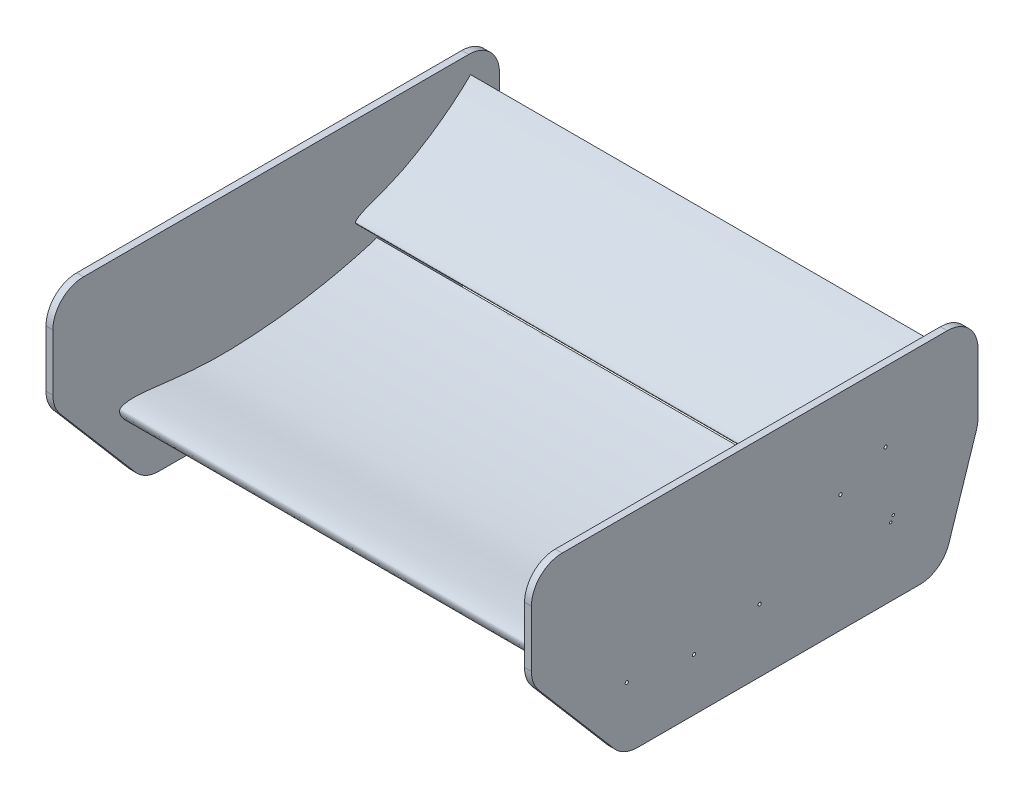
SolidWorks part; units mm, degrees
ref_plane "Front Plane" through (0, 0, 0) normal (0, 0, 1) x (1, 0, 0)
ref_plane "Top Plane" through (0, 0, 0) normal (0, 1, 0) x (1, 0, 0)
ref_plane "Right Plane" through (0, 0, 0) normal (1, 0, 0) x (0, 0, -1)
ref_plane "Soft Top Limit" through (0, 1174.6, 0) normal (0, 1, 0) x (1, 0, 0)
ref_plane "Soft Rear Limit" through (0, 0, -1192.975) normal (0, 0, 1) x (1, 0, 0)
ref_plane "Soft Right Limit" through (-501.65, 0, 0) normal (1, 0, 0) x (0, 0, -1)
ref_plane "Soft Left Limit" through (501.65, 0, 0) normal (1, 0, 0) x (0, 0, -1)
ref_plane "Soft Front Limit" through (0, 0, -165.1) normal (0, 0, 1) x (1, 0, 0)
ref_plane "Slant Limit" through (0, 528.6251, -619.2711) normal (0, -0.6492, 0.7606) x (1, 0, 0)
ref_plane "Bottom" through (0, 476.25, 0) normal (0, 1, 0) x (1, 0, 0)
ref_plane "Midplane" through (0, 0, 0) normal (1, 0, 0) x (0, 0, -1)
curve "Imported Airfoil Curve"
  spline degree 3 poles (0, 2520.0207, 6.126) (0, 2544.889, -1.81) (0, 2521.8965, 7.8839) (0, 2505.3253, 17.7145) (0, 2467.7144, 38.5723) (0, 2424.2142, 62.3813) (0, 2368.0949, 87.8078) (0, 2301.3729, 113.3478) (0, 2223.8362, 140.5377) (0, 2136.6129, 169.2441) (0, 2040.932, 199.097) (0, 1938.2341, 229.6055) (0, 1829.9414, 260.0781) (0, 1717.5266, 289.8586) (0, 1602.4273, 318.1375) (0, 1486.0259, 343.9752) (0, 1369.6902, 366.5754) (0, 1254.3666, 384.7865) (0, 1140.5393, 397.0034) (0, 1028.6357, 403.0127) (0, 919.0585, 402.9406) (0, 812.3986, 397.0375) (0, 709.2785, 385.5985) (0, 610.4299, 369.039) (0, 516.5862, 348.1086) (0, 428.5874, 323.3415) (0, 347.2653, 295.2055) (0, 273.332, 264.2656) (0, 207.4209, 231.0894) (0, 150.0337, 196.3024) (0, 101.596, 160.572) (0, 62.3674, 124.65) (0, 32.4977, 89.3959) (0, 12.0597, 55.6746) (0, 1.683, 26.6201) (0, -0.5567, 6.5526) (0, 0.5894, -3.9947) (0, 1.6947, -9.1451) (0, 2.8711, -12.4915) (0, 3.9449, -14.9776) (0, 4.8993, -16.669) (0, 5.9763, -18.2433) (0, 7.3264, -19.6365) (0, 8.8595, -20.9434) (0, 11.1868, -22.7306) (0, 14.6073, -24.7406) (0, 20.085, -27.4067) (0, 26.8353, -29.9257) (0, 44.6446, -35.1819) (0, 77.8093, -38.8998) (0, 130.2841, -38.2927) (0, 196.3018, -31.4611) (0, 276.2192, -18.4434) (0, 370.8288, 0.8611) (0, 480.7331, 24.811) (0, 605.9792, 50.0099) (0, 745.0759, 74.1542) (0, 895.4497, 95.0846) (0, 1053.6786, 110.004) (0, 1215.6439, 118.3392) (0, 1377.6893, 121.6348) (0, 1537.1174, 120.5125) (0, 1691.5141, 115.2051) (0, 1838.3121, 105.7388) (0, 1975.028, 93.0069) (0, 2099.5942, 78.4581) (0, 2210.5746, 63.1262) (0, 2306.3634, 48.0168) (0, 2387.2069, 33.7158) (0, 2449.0745, 22.0129) (0, 2499.1865, 10.4993) (0, 2520.0207, 6.126) (0, 2544.889, -1.81) (0, 2521.8965, 7.8839) knots -0.016237 -0.007308 -0.001841 0 0.001813 0.006911 0.014576 0.024172 0.035572 0.049013 0.064513 0.081849 0.100772 0.120997 0.142228 0.164173 0.186537 0.209023 0.231367 0.25332 0.274804 0.295858 0.316449 0.336531 0.356033 0.374893 0.39299 0.410197 0.426388 0.441459 0.455334 0.467938 0.479236 0.489204 0.497851 0.505194 0.511308 0.515097 0.516441 0.517273 0.51806 0.518436 0.518797 0.519154 0.519508 0.519887 0.520289 0.52116 0.522116 0.52372 0.525214 0.532575 0.542381 0.554776 0.569931 0.588005 0.609188 0.633329 0.660001 0.688743 0.718873 0.749543 0.780127 0.810209 0.839387 0.867183 0.893104 0.91676 0.937874 0.956199 0.971544 0.983763 0.992692 0.998159 1 1.001813 1.006911 1.014576 periodic
sketch "Airfoils Sketch" plane through (0, 0, 0) normal (1, 0, 0) x (0, 0, -1)
  line L0 (165.1, 1174.6) -> (165.1, 1060.6753) construction
  line L1 (165.1, 1060.6753) -> (663.9798, 476.25) construction
  line L2 (663.9798, 476.25) -> (1192.975, 476.25) construction
  line L3 (1192.975, 476.25) -> (1192.975, 1174.6) construction
  line L4 (1192.975, 1174.6) -> (165.1, 1174.6) construction
  line L5 (509.9361, 1174.6) -> (-509.9361, 1174.6) construction
  line L6 (165.1, 67.0076) -> (165.1, -67.0076) construction
  line L7 (364.7288, 826.8151) -> (873.8134, 230.4351) construction
  line L8 (279.3831, 476.25) -> (-279.3831, 476.25) construction
  line L9 (1192.975, 353.2696) -> (1192.975, -353.2696) construction
  line L10 (414.7055, 818.0274) -> (401.202, 972.3726) construction
  line L11 (945.202, 874.5029) -> (933.446, 1008.8748) construction
  line L12 (939.324, 941.6889) -> (407.9538, 895.2) construction
  line L13 (306.3538, 895.2) -> (1192.975, 895.2) construction
  line L14 (866.0383, 1036.8746) -> (926.5682, 940.0065) construction
  line L15 (1102.685, 1185.4108) -> (1163.8108, 1087.5892) construction
  line L16 (1133.2479, 1136.5) -> (896.3033, 988.4406) construction
  line L21 (176.2614, 1047.6) -> (1192.975, 1047.6) construction
  spline S0 degree 3 poles (935.2529, 940.0507) (940.3147, 942.1548) (935.6767, 939.7163) (932.3848, 937.3638) (924.8872, 932.3286) (916.21, 926.5709) (904.9213, 920.2497) (891.4161, 913.7156) (875.6775, 906.6433) (857.9391, 899.0809) (838.4515, 891.1278) (817.5075, 882.9123) (795.3921, 874.6046) (772.4019, 866.3681) (748.8232, 858.3979) (724.9284, 850.9153) (700.9897, 844.1113) (677.1845, 838.2437) (653.5854, 833.657) (630.2782, 830.4035) (607.3492, 828.4639) (584.9266, 827.7965) (563.1459, 828.3505) (542.1676, 830.0521) (522.1586, 832.7575) (503.3041, 836.37) (485.7865, 840.8065) (469.765, 845.9615) (455.382, 851.7275) (442.7539, 857.9825) (431.9816, 864.5947) (423.1327, 871.4111) (416.2539, 878.2548) (411.376, 884.946) (408.6865, 890.8402) (407.8599, 894.9991) (407.9116, 897.2265) (408.051, 898.3239) (408.2374, 899.0451) (408.4178, 899.5844) (408.5873, 899.9553) (408.7846, 900.3039) (409.0422, 900.6195) (409.3397, 900.9203) (409.7947, 901.3358) (410.4746, 901.8174) (411.5732, 902.4729) (412.9407, 903.1204) (416.5733, 904.5379) (423.4463, 905.9074) (434.4368, 906.7165) (448.3721, 906.4646) (465.3261, 905.1664) (485.4664, 902.8148) (508.8897, 899.7641) (535.5455, 896.7257) (565.0805, 894.155) (596.9177, 892.4579) (630.2914, 892.1587) (664.3294, 893.3038) (698.2942, 895.5048) (731.6326, 898.5836) (763.8436, 902.4482) (794.3904, 907.0475) (822.7695, 912.1503) (848.5739, 917.4165) (871.5218, 922.6042) (891.2949, 927.4743) (907.9553, 931.9087) (920.6916, 935.461) (930.9716, 938.764) (935.2529, 940.0507) (940.3147, 942.1548) (935.6767, 939.7163) knots -0.016237 -0.007308 -0.001841 0 0.001813 0.006911 0.014576 0.024172 0.035572 0.049013 0.064513 0.081849 0.100772 0.120997 0.142228 0.164173 0.186537 0.209023 0.231367 0.25332 0.274804 0.295858 0.316449 0.336531 0.356033 0.374893 0.39299 0.410197 0.426388 0.441459 0.455334 0.467938 0.479236 0.489204 0.497851 0.505194 0.511308 0.515097 0.516441 0.517273 0.51806 0.518436 0.518797 0.519154 0.519508 0.519887 0.520289 0.52116 0.522116 0.52372 0.525214 0.532575 0.542381 0.554776 0.569931 0.588005 0.609188 0.633329 0.660001 0.688743 0.718873 0.749543 0.780127 0.810209 0.839387 0.867183 0.893104 0.91676 0.937874 0.956199 0.971544 0.983763 0.992692 0.998159 1 1.001813 1.006911 1.014576 only from (939.324, 941.6889) to (939.324, 941.6889)
  spline S1 degree 3 poles (1131.7374, 1134.7673) (1133.5995, 1136.953) (1132.0147, 1134.712) (1131.0377, 1132.8312) (1128.7359, 1128.6983) (1126.0553, 1123.9476) (1122.2899, 1118.3128) (1117.5406, 1112.0516) (1111.8769, 1105.0082) (1105.3965, 1097.2604) (1098.1926, 1088.9143) (1090.3713, 1080.0994) (1082.0253, 1070.9629) (1073.254, 1061.6516) (1064.1447, 1052.3247) (1054.7721, 1043.1501) (1045.2175, 1034.2818) (1035.5025, 1025.8823) (1025.5791, 1018.1297) (1015.4749, 1011.0686) (1005.2348, 1004.7108) (994.9285, 999.0671) (984.6313, 994.1461) (974.4357, 989.9515) (964.4538, 986.456) (954.795, 983.6583) (945.5642, 981.5631) (936.8608, 980.159) (928.7768, 979.4298) (921.3956, 979.3461) (914.7955, 979.8704) (909.0446, 980.9475) (904.2067, 982.5058) (900.3389, 984.4687) (897.682, 986.58) (896.3072, 988.3245) (895.8017, 989.3763) (895.6058, 989.9216) (895.5213, 990.3026) (895.4772, 990.5972) (895.4681, 990.8106) (895.4773, 991.0202) (895.5225, 991.2288) (895.5898, 991.4399) (895.7034, 991.742) (895.9061, 992.1285) (896.263, 992.6957) (896.7472, 993.3231) (898.1055, 994.8485) (900.9876, 997.1221) (905.9247, 1000.1133) (912.4884, 1003.3096) (920.7099, 1006.7355) (930.6689, 1010.4274) (942.3265, 1014.5737) (955.4898, 1019.4945) (969.8856, 1025.3183) (985.1482, 1032.0973) (1000.7954, 1039.894) (1016.4092, 1048.5229) (1031.7378, 1057.6271) (1046.5653, 1066.992) (1060.6797, 1076.4556) (1073.8427, 1085.8664) (1085.8742, 1094.9966) (1096.6653, 1103.5909) (1106.1418, 1111.4691) (1114.2121, 1118.4443) (1120.9333, 1124.4758) (1126.0328, 1129.1625) (1130.0452, 1133.1487) (1131.7374, 1134.7673) (1133.5995, 1136.953) (1132.0147, 1134.712) knots -0.016237 -0.007308 -0.001841 0 0.001813 0.006911 0.014576 0.024172 0.035572 0.049013 0.064513 0.081849 0.100772 0.120997 0.142228 0.164173 0.186537 0.209023 0.231367 0.25332 0.274804 0.295858 0.316449 0.336531 0.356033 0.374893 0.39299 0.410197 0.426388 0.441459 0.455334 0.467938 0.479236 0.489204 0.497851 0.505194 0.511308 0.515097 0.516441 0.517273 0.51806 0.518436 0.518797 0.519154 0.519508 0.519887 0.520289 0.52116 0.522116 0.52372 0.525214 0.532575 0.542381 0.554776 0.569931 0.588005 0.609188 0.633329 0.660001 0.688743 0.718873 0.749543 0.780127 0.810209 0.839387 0.867183 0.893104 0.91676 0.937874 0.956199 0.971544 0.983763 0.992692 0.998159 1 1.001813 1.006911 1.014576 only from (1133.2479, 1136.5) to (1133.2479, 1136.5)
  dimension "D1" = 533.4
  dimension "D2" = 279.4
  dimension "D3" = 5
  dimension "D4" = 101.6
  dimension "D5" = 279.4
  dimension "D6" = 38.1
  dimension "D7" = 32
extrude "Extruded Airfoils" add sketch "Airfoils Sketch" along normal offset from surface (487.45 mm away) 14.2 up to plane "Soft Left Limit"
sketch "Endplate Sketch" plane through (501.65, 0, 0) normal (1, 0, 0) x (0, 0, -1)
  line L6 (333.4477, 1174.6) -> (1129.475, 1174.6)
  line L7 (1192.975, 1174.6) -> (165.1, 1174.6) construction
  line L8 (1192.975, 1111.1) -> (1192.975, 986.6717)
  line L9 (1192.975, 476.25) -> (1192.975, 1174.6) construction
  line L11 (1189.8464, 966.9854) -> (1132.8969, 792.34)
  line L12 (1072.5255, 748.5263) -> (489.1772, 748.5263)
  line L19 (440.8805, 770.7991) -> (285.151, 953.2323)
  line L26 (269.9477, 994.4595) -> (269.9477, 1111.1)
  line L28 (165.1, 1060.6753) -> (663.9798, 476.25) construction
  arc A12 (1129.475, 1174.6) -> (1192.975, 1111.1) centre (1129.475, 1111.1) cw
  arc A13 (1192.975, 986.6717) -> (1189.8464, 966.9854) centre (1129.475, 986.6717) cw
  arc A14 (1132.8969, 792.34) -> (1072.5255, 748.5263) centre (1072.5255, 812.0263) cw
  arc A15 (489.1772, 748.5263) -> (440.8805, 770.7991) centre (489.1772, 812.0263) cw
  arc A16 (285.151, 953.2323) -> (269.9477, 994.4595) centre (333.4477, 994.4595) cw
  arc A17 (333.4477, 1174.6) -> (269.9477, 1111.1) centre (333.4477, 1111.1) ccw
  point P16 (1192.975, 1174.6)
  point P19 (1192.975, 976.5799)
  point P29 (269.9477, 1174.6)
  dimension "D1" = 63.5
extrude "Extruded Endplate" add sketch "Endplate Sketch" against normal up to surface (14.2 mm away)
mirror "Mirror" about plane through (0, 0, 0) normal (1, 0, 0) of bodies 106
sketch "Sketch1" plane through (501.65, 0, 0) normal (1, 0, 0) x (0, 0, -1)
  circle A0 centre (466.9636, 876.0274) radius 3.302
  point P2 (466.9636, 876.0274)
extrude "Cut-Extrude1" cut sketch "Sketch1" against normal up to surface (14.2 mm away) up to face at (487.45, 961.8886, -750.0842)
sketch "Sketch2" plane through (501.65, 0, 0) normal (1, 0, 0) x (0, 0, -1)
  circle A0 centre (605.9718, 856.7319) radius 3.302
  point P2 (605.9718, 856.7319)
extrude "Cut-Extrude2" cut sketch "Sketch2" against normal up to surface (14.2 mm away) up to face at (487.45, 961.8886, -750.0842)
sketch "Sketch3" plane through (501.65, 0, 0) normal (1, 0, 0) x (0, 0, -1)
  circle A0 centre (741.5917, 878.9853) radius 3.302
  circle A1 centre (908.6976, 991.5292) radius 3.302
  circle A2 centre (1002.03, 1029.97) radius 3.302
  point P2 (1002.03, 1029.4449)
  point P7 (1008.523, 1027.663)
  point P8 (996.0963, 1026.316)
  point P9 (1002.03, 1029.97)
extrude "Cut-Extrude3" cut sketch "Sketch3" against normal up to surface (14.2 mm away) up to face at (487.45, 961.8886, -750.0842)
sketch "Sketch4" plane through (501.65, 0, 0) normal (1, 0, 0) x (0, 0, -1)
  circle A0 centre (1018.0658, 900.3059) radius 2.54
  circle A1 centre (1012.4254, 889.9969) radius 2.54
  point P4 (1012.4254, 889.9969)
  point P5 (1032.5446, 900.3059)
  point P6 (1030.5946, 900.3059)
  point P7 (1018.0658, 900.3059)
extrude "Cut-Extrude4" cut sketch "Sketch4" against normal up to surface (14.2 mm away) up to face at (487.45, 961.8886, -750.0842)
